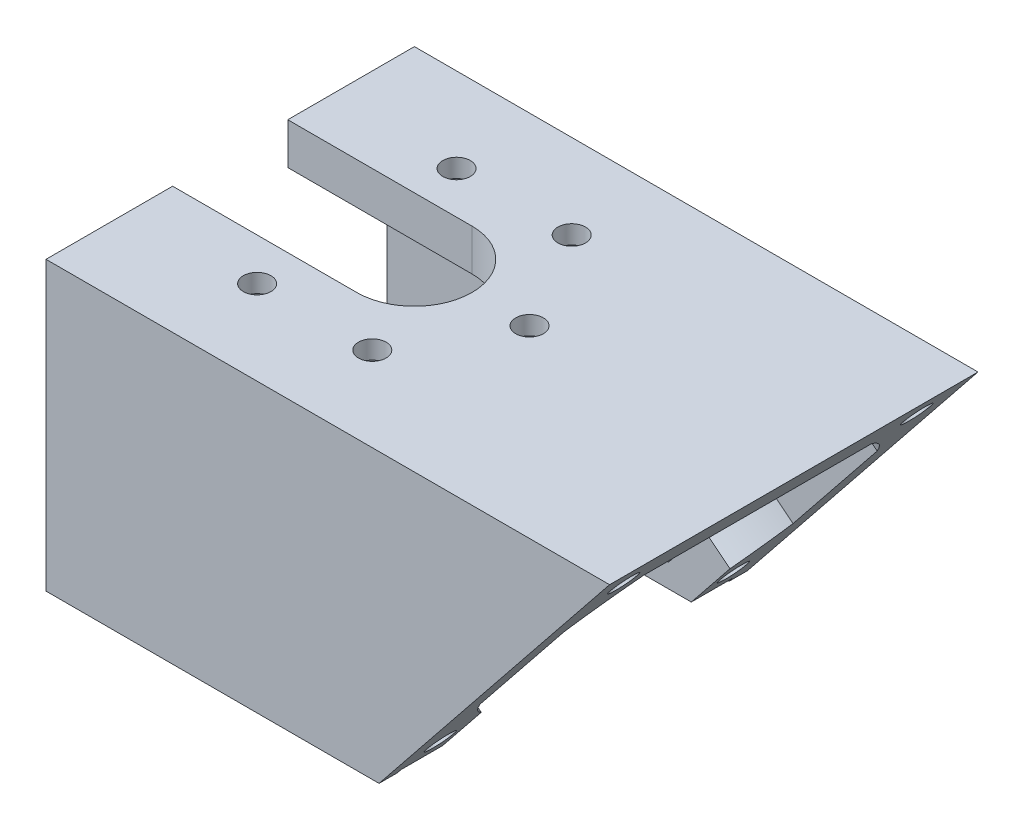
SolidWorks part; units mm, degrees
ref_plane "Front Plane" through (0, 0, 0) normal (0, 0, 1) x (1, 0, 0)
ref_plane "Top Plane" through (0, 0, 0) normal (0, 1, 0) x (1, 0, 0)
ref_plane "Right Plane" through (0, 0, 0) normal (1, 0, 0) x (0, 0, -1)
sketch "Sketch1" plane through (0, 0, 0) normal (0, 0, 1) x (1, 0, 0)
  line L0 (-20, -4.8) -> (41.1912, -4.8)
  line L1 (41.1912, -4.8) -> (16.16, -36)
  line L2 (16.16, -36) -> (-20, -36)
  line L3 (-20, -4.8) -> (-20, -36)
  line L4 (-11.8, -37) -> (6.16, -37) construction
  line L5 (6.16, -46.4) -> (6.16, -37.2) construction
  dimension "D1" = 40
  dimension "D2" = 1
  dimension "D3" = 20
  dimension "D4" = 10
extrude "Boss-Extrude1" add sketch "Sketch1" along normal blind 20 and the other way blind 20
sketch "Sketch2" plane through (27.4036, -21.9854, 0) normal (0.78, -0.6258, 0) x (0, 0, -1)
  line L0 (-20, 22.0326) -> (20, -17.9674) construction
  line L1 (0, 2.0326) -> (-11.2848, 2.0326) construction
  line L2 (0, 0) -> (0, -9.4753) construction
  circle A0 centre (0, 2.0326) radius 18.5
  circle A1 centre (-15.9099, -13.8773) radius 1.5
  circle A2 centre (-15.9099, 17.9425) radius 1.5
  circle A3 centre (15.9099, 17.9425) radius 1.5
  circle A4 centre (15.9099, -13.8773) radius 1.5
  dimension "D1" = 37
  dimension "D3" = 3
  dimension "D2" = 45
sketch "Sketch3" plane through (-20, 0, 0) normal (-1, 0, 0) x (0, 0, 1)
  line L8 (-17, -33) -> (17, -33)
  line L9 (17, -33) -> (17, -7.8)
  line L10 (17, -7.8) -> (-17, -7.8)
  line L11 (-17, -7.8) -> (-17, -33)
  line L12 (-17, -33) -> (17, -33)
  line L13 (17, -33) -> (17, -7.8)
  line L14 (17, -7.8) -> (-17, -7.8)
  line L15 (-17, -7.8) -> (-17, -33)
  dimension "D1" = 3
extrude "Cut-Extrude1" cut sketch "Sketch3" against normal offset from surface (54.9382 mm away) 3 up to face at (28.6756, -20.4, 0)
sketch "Sketch4" plane through (25.0636, -20.1081, 0) normal (-0.78, 0.6258, 0) x (0, 0, 1)
  line L0 (-17, 15.7796) -> (-17, -16.5281) construction
  line L1 (17, 15.7796) -> (-17, 15.7796) construction
  line L2 (17, -16.5281) -> (17, 15.7796) construction
  line L4 (-17, 9.3299) -> (-17, -5.2647)
  line L5 (12.3802, 15.7796) -> (-12.3802, 15.7796)
  line L6 (17, -5.2647) -> (17, 9.3299)
  circle A0 centre (0, 2.0326) radius 18.5 construction
  arc A1 (-17, -5.2647) -> (17, -5.2647) centre (0, 2.0326) ccw
  arc A2 (17, 9.3299) -> (12.3802, 15.7796) centre (0, 2.0326) ccw
  arc A3 (-12.3802, 15.7796) -> (-17, 9.3299) centre (0, 2.0326) ccw
extrude "Cut-Extrude2" cut sketch "Sketch4" against normal up to surface (3 mm away) up to face at (28.6756, -20.4, 0)
sketch "Sketch5" plane through (0, -4.8, 0) normal (0, 1, 0) x (1, 0, 0)
  line L0 (0, 6.25) -> (-20, 6.25)
  line L1 (-20, 20) -> (-20, -20) construction
  line L2 (0, -6.25) -> (-20, -6.25)
  line L3 (-20, 6.25) -> (-20, -6.25)
  arc A0 (0, -6.25) -> (0, 6.25) centre (0, 0) ccw
  dimension "D1" = 12.5
extrude "Cut-Extrude3" cut sketch "Sketch5" against normal up to next
sketch "Sketch7" plane through (0, -4.8, 0) normal (0, 1, 0) x (1, 0, 0)
  line L0 (0, 0) -> (12.5, 0) construction
  circle A0 centre (12.5, 0) radius 1.5
  circle A1 centre (6.25, -10.8253) radius 1.5
  circle A2 centre (-6.25, -10.8253) radius 1.5
  circle A3 centre (-12.5, 0) radius 1.5
  circle A4 centre (-6.25, 10.8253) radius 1.5
  circle A5 centre (6.25, 10.8253) radius 1.5
  point P16 (0, 0)
  dimension "D1" = 3
  dimension "D3" = 25
  dimension "D2" = 6
extrude "Cut-Extrude4" cut sketch "Sketch7" against normal up to surface (31.2 mm away) up to face at (-1.92, -36, 0)
sketch "Sketch6" plane through (0, -7.8, 0) normal (0, -1, 0) x (1, 0, 0)
  line L0 (0, 6.25) -> (-17.2097, 6.25)
  line L2 (0, 6.25) -> (-20, 6.25) construction
  line L3 (0, -6.25) -> (-17.2097, -6.25)
  line L4 (0, 18.3095) -> (-20, 18.3095)
  line L5 (-20, 6.25) -> (-20, 20) construction
  line L6 (-20, 18.3095) -> (-20, 6.25)
  line L7 (-20, 6.25) -> (-17.2097, 6.25)
  line L8 (0, 0) -> (-5.2384, 0) construction
  line L9 (-20, -6.25) -> (-17.2097, -6.25)
  line L10 (-20, -18.3095) -> (-20, -6.25)
  line L11 (0, -18.3095) -> (-20, -18.3095)
  circle A0 centre (-6.25, 10.8253) radius 1.5 construction
  circle A1 centre (6.25, 10.8253) radius 1.5 construction
  circle A2 centre (12.5, 0) radius 1.5 construction
  circle A3 centre (6.25, -10.8253) radius 1.5 construction
  circle A4 centre (-6.25, -10.8253) radius 1.5 construction
  arc A5 (0, -6.25) -> (0, 6.25) centre (0, 0) ccw
  arc A6 (0, -18.3095) -> (0, 18.3095) centre (0, 0) ccw
  circle A7 centre (-6.25, 10.8253) radius 1.5
  circle A8 centre (6.25, 10.8253) radius 1.5
  circle A9 centre (12.5, 0) radius 1.5
  circle A10 centre (6.25, -10.8253) radius 1.5
  circle A11 centre (-6.25, -10.8253) radius 1.5
extrude "Boss-Extrude2" add sketch "Sketch6" along normal blind 1.5
chamfer "Chamfer3" distance 1.5 angle 45 1 edges at (18.3095, -7.8, 0)
sketch "Sketch8" plane through (0, -9.3, 0) normal (0, -1, 0) x (1, 0, 0)
  line L1 (12.5, 3.1754) -> (9.75, 1.5877)
  line L2 (9.75, 1.5877) -> (9.75, -1.5877)
  line L3 (9.75, -1.5877) -> (12.5, -3.1754)
  line L4 (12.5, -3.1754) -> (15.25, -1.5877)
  line L5 (15.25, -1.5877) -> (15.25, 1.5877)
  line L6 (15.25, 1.5877) -> (12.5, 3.1754)
  line L7 (9.4254, 10.8253) -> (7.8377, 13.5753)
  line L8 (7.8377, 13.5753) -> (4.6623, 13.5753)
  line L9 (4.6623, 13.5753) -> (3.0746, 10.8253)
  line L10 (3.0746, 10.8253) -> (4.6623, 8.0753)
  line L11 (4.6623, 8.0753) -> (7.8377, 8.0753)
  line L12 (7.8377, 8.0753) -> (9.4254, 10.8253)
  line L13 (-3.0746, 10.8253) -> (-4.6623, 13.5753)
  line L14 (-4.6623, 13.5753) -> (-7.8377, 13.5753)
  line L15 (-7.8377, 13.5753) -> (-9.4254, 10.8253)
  line L16 (-9.4254, 10.8253) -> (-7.8377, 8.0753)
  line L17 (-7.8377, 8.0753) -> (-4.6623, 8.0753)
  line L18 (-4.6623, 8.0753) -> (-3.0746, 10.8253)
  line L19 (-3.0746, -10.8253) -> (-4.6623, -8.0753)
  line L20 (-4.6623, -8.0753) -> (-7.8377, -8.0753)
  line L21 (-7.8377, -8.0753) -> (-9.4254, -10.8253)
  line L22 (-9.4254, -10.8253) -> (-7.8377, -13.5753)
  line L23 (-7.8377, -13.5753) -> (-4.6623, -13.5753)
  line L24 (-4.6623, -13.5753) -> (-3.0746, -10.8253)
  line L25 (9.4254, -10.8253) -> (7.8377, -8.0753)
  line L26 (7.8377, -8.0753) -> (4.6623, -8.0753)
  line L27 (4.6623, -8.0753) -> (3.0746, -10.8253)
  line L28 (3.0746, -10.8253) -> (4.6623, -13.5753)
  line L29 (4.6623, -13.5753) -> (7.8377, -13.5753)
  line L30 (7.8377, -13.5753) -> (9.4254, -10.8253)
  circle A0 centre (12.5, 0) radius 2.75 construction
  circle A1 centre (6.25, 10.8253) radius 2.75 construction
  circle A2 centre (-6.25, 10.8253) radius 2.75 construction
  circle A3 centre (-6.25, -10.8253) radius 2.75 construction
  circle A4 centre (6.25, -10.8253) radius 2.75 construction
  dimension "D1" = 5.5
extrude "Cut-Extrude5" cut sketch "Sketch8" against normal offset from surface (2.5 mm away) 2 up to face at (4.75, -4.8, -10.8253)
sketch "Sketch9" plane through (0, -33, 0) normal (0, 1, 0) x (1, 0, 0)
  line L0 (-20, 13.5) -> (24.906, 13.5)
  line L1 (-20, 17) -> (-20, -17) construction
  line L2 (24.906, 13.5) -> (24.906, -13.5)
  line L3 (-20, 0) -> (-29.9674, 0) construction
  line L4 (-20, 13.5) -> (-20, -13.5)
  line L5 (-20, -13.5) -> (24.906, -13.5)
  line L6 (14.7207, 17) -> (-20, 17) construction
  point P10 (24.906, 0)
  dimension "D1" = 3.5
extrude "Cut-Extrude6" cut sketch "Sketch9" against normal up to next and the other way up to next
sketch "Sketch10" plane through (25.0636, -20.1081, 0) normal (-0.78, 0.6258, 0) x (0, 0, 1)
  line L0 (17, 9.3299) -> (17, 15.7796) construction
  line L1 (17, 15.7796) -> (12.3802, 15.7796) construction
  line L2 (-12.3802, 15.7796) -> (-17, 15.7796) construction
  line L3 (-17, 15.7796) -> (-17, 9.3299) construction
  line L4 (17, 9.3299) -> (17, 15.7796)
  line L5 (17, 15.7796) -> (12.3802, 15.7796)
  line L6 (-12.3802, 15.7796) -> (-17, 15.7796)
  line L7 (-17, 15.7796) -> (-17, 9.3299)
  arc A0 (17, 9.3299) -> (12.3802, 15.7796) centre (0, 2.0326) ccw construction
  arc A1 (-12.3802, 15.7796) -> (-17, 9.3299) centre (0, 2.0326) ccw construction
  arc A2 (17, 9.3299) -> (12.3802, 15.7796) centre (0, 2.0326) ccw
  arc A3 (-12.3802, 15.7796) -> (-17, 9.3299) centre (0, 2.0326) ccw
extrude "Boss-Extrude3" add sketch "Sketch10" along normal up to next
chamfer "Chamfer1" distance 4 angle 45 2 edges at (18.2449, -28.6073, -17) (18.2449, -28.6073, 17)
chamfer "Chamfer2" distance 3.5 angle 45 2 edges at (-5.2038, -33, -17) (-5.2038, -33, 17)
sketch "Sketch11" plane through (0, -36, 0) normal (0, -1, 0) x (1, 0, 0)
  line L0 (-20, 13.5) -> (-20, 18)
  line L1 (-20, 13.5) -> (-20, 20) construction
  line L2 (-20, 18) -> (20.5056, 18)
  line L3 (20.5056, 18) -> (20.5056, 13.5)
  line L4 (20.76, 13.5) -> (16.16, 13.5) construction
  line L5 (20.5056, 13.5) -> (-20, 13.5)
  line L6 (20.5056, -18) -> (20.5056, -13.5)
  line L7 (0, 0) -> (-7.504, 0) construction
  line L8 (-20, -18) -> (20.5056, -18)
  line L9 (-20, -13.5) -> (-20, -18)
  line L10 (20.5056, -13.5) -> (-20, -13.5)
  line L11 (-20, 20) -> (16.16, 20) construction
  dimension "D1" = 2
extrude "Cut-Extrude7" cut sketch "Sketch11" against normal blind 0.5
sketch "Sketch13" plane through (27.4036, -21.9854, 0) normal (0.78, -0.6258, 0) x (0, 0, -1)
  circle A0 centre (-15.9099, 17.9425) radius 1.5 construction
  circle A1 centre (15.9099, 17.9425) radius 1.5 construction
  circle A2 centre (15.9099, -13.8773) radius 1.5 construction
  circle A3 centre (-15.9099, -13.8773) radius 1.5 construction
  circle A4 centre (-15.9099, 17.9425) radius 1.5
  circle A5 centre (15.9099, 17.9425) radius 1.5
  circle A6 centre (15.9099, -13.8773) radius 1.5
  circle A7 centre (-15.9099, -13.8773) radius 1.5
extrude "Cut-Extrude8" cut sketch "Sketch13" against normal blind 3.15
